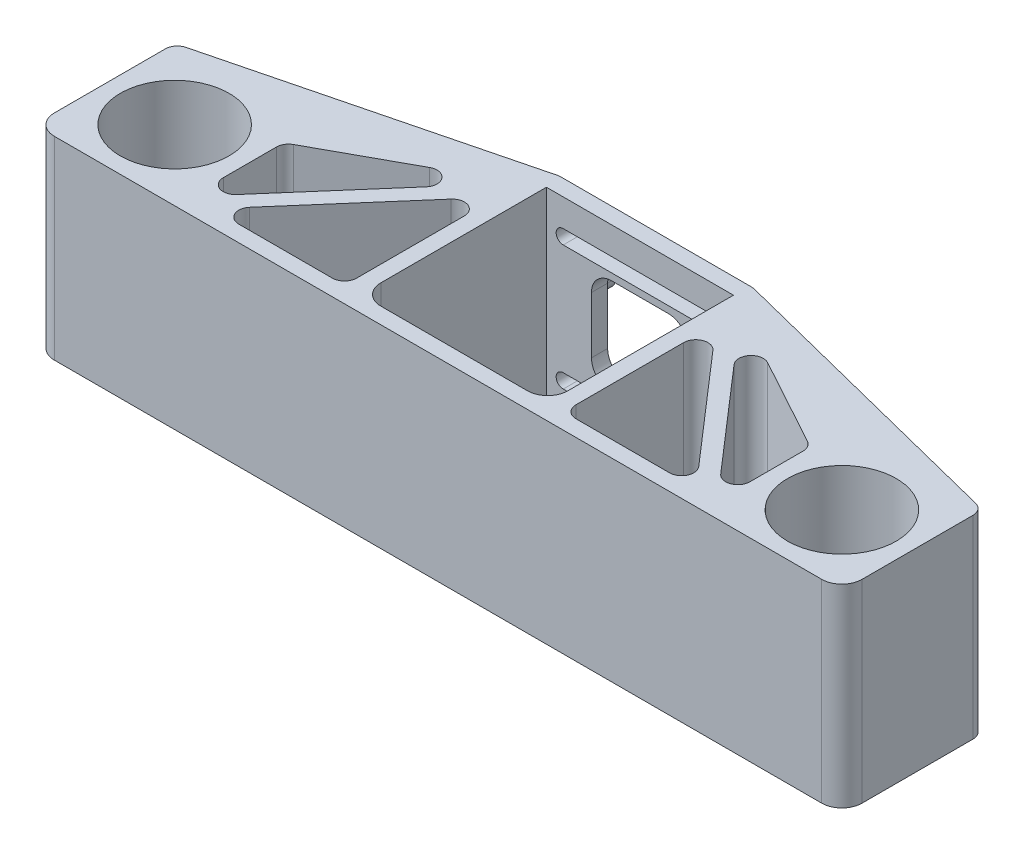
SolidWorks part; units mm, degrees
ref_plane "Front Plane" through (0, 0, 0) normal (0, 0, 1) x (1, 0, 0)
ref_plane "Top Plane" through (0, 0, 0) normal (0, 1, 0) x (1, 0, 0)
ref_plane "Right Plane" through (0, 0, 0) normal (1, 0, 0) x (0, 0, -1)
sketch "Sketch2" plane through (0, 0, 0) normal (0, 1, 0) x (1, 0, 0)
  line L0 (-17.4, -17.4) -> (82.6, -17.4) construction
  line L1 (-17.4, -17.4) -> (17.4, -17.4)
  line L2 (-17.4, -17.4) -> (-17.4, 17.4)
  line L5 (0, 17.4) -> (0, -17.4) construction
  line L6 (-17.4, 0) -> (17.4, 9.5816) construction
  line L7 (82.6, -17.4) -> (82.6, 36.6) construction
  line L8 (17.4, -13.4) -> (17.4, 9.5816)
  line L9 (82.6, 36.6) -> (58.6, 36.6)
  line L10 (82.6, 36.6) -> (82.6, 32.6)
  line L11 (82.6, 32.6) -> (59.447, 32.6)
  line L13 (17.4, 9.5816) -> (55.447, 30.4102)
  line L14 (58.6, 36.6) -> (-17.4, 17.4)
  line L15 (17.4, -17.4) -> (82.6, -17.4)
  line L16 (82.6, -17.4) -> (82.6, -13.4)
  line L17 (82.6, -13.4) -> (59.447, -13.4)
  line L18 (59.447, 32.6) -> (59.447, -13.4)
  line L20 (55.447, -13.4) -> (55.447, 24.3099)
  line L22 (55.447, 30.4102) -> (17.4, -13.4)
  line L23 (22.6979, -13.4) -> (55.447, 24.3099)
  line L24 (55.447, -13.4) -> (22.6979, -13.4)
  circle A0 centre (0, 0) radius 13.45
  point P0 (0, 0)
  dimension "D3" = 26.9
  dimension "D8" = 17.4
  dimension "D9" = 17.4
  dimension "D1" = 34.8
  dimension "D2" = 34.8
  dimension "D4" = 100
  dimension "D5" = 54
  dimension "D6" = 24
  dimension "D7" = 4
  dimension "D10" = 4
  dimension "D11" = 4
  dimension "D12" = 4
extrude "Boss-Extrude1" add sketch "Sketch2" along normal blind 48
sketch3d "3DSketch1"
  line L0 (82.6, 0, -36.6) -> (82.6, 0, -32.6) construction
  line L1 (82.6, 0, -32.6) -> (82.6, 48, -32.6) construction
ref_plane "Plane1" through (82.6, 0, 0) normal (1, 0, 0) x (0, 0, -1)
mirror "Mirror1" about plane through (82.6, 0, 0) normal (1, 0, 0) of "Boss-Extrude1"
sketch "Sketch4" plane through (0, 0, -36.6) normal (0, 0, -1) x (-1, 0, 0)
  line L0 (-106.6, 24) -> (-58.6, 24) construction
  line L1 (-58.6, 48) -> (-58.6, 0) construction
  line L2 (-101.6, 8.55) -> (-63.6, 8.55) construction
  line L3 (-101.6, 10.3) -> (-63.6, 10.3)
  line L4 (-82.6, 0) -> (-82.6, 48) construction
  line L5 (-101.6, 6.8) -> (-63.6, 6.8)
  line L6 (-101.6, 39.45) -> (-63.6, 39.45) construction
  line L7 (-101.6, 37.7) -> (-63.6, 37.7)
  line L8 (-101.6, 41.2) -> (-63.6, 41.2)
  line L10 (-89.6, 12) -> (-75.6, 12)
  line L11 (-94.6, 17) -> (-94.6, 31)
  line L12 (-89.6, 36) -> (-75.6, 36)
  line L13 (-70.6, 17) -> (-70.6, 31)
  line L14 (-94.6, 12) -> (-70.6, 36) construction
  line L15 (-94.6, 36) -> (-70.6, 12) construction
  arc A0 (-101.6, 10.3) -> (-101.6, 6.8) centre (-101.6, 8.55) ccw
  arc A1 (-63.6, 6.8) -> (-63.6, 10.3) centre (-63.6, 8.55) ccw
  arc A2 (-101.6, 37.7) -> (-101.6, 41.2) centre (-101.6, 39.45) cw
  arc A3 (-63.6, 41.2) -> (-63.6, 37.7) centre (-63.6, 39.45) cw
  arc A5 (-94.6, 17) -> (-89.6, 12) centre (-89.6, 17) ccw
  arc A6 (-75.6, 12) -> (-70.6, 17) centre (-75.6, 17) ccw
  arc A7 (-70.6, 31) -> (-75.6, 36) centre (-75.6, 31) ccw
  arc A8 (-94.6, 31) -> (-89.6, 36) centre (-89.6, 31) cw
  circle A9 centre (-82.6, 24) radius 12 construction
  point P5 (-82.6, 24)
  point P7 (-82.6, 8.55)
  point P10 (-82.6, 24)
  point P17 (-82.6, 39.45)
  dimension "D4" = 24
  dimension "D6" = 5
  dimension "D1" = 15.45
  dimension "D2" = 1.75
  dimension "D3" = 38
  dimension "D5" = 24
extrude "Cut-Extrude1" cut sketch "Sketch4" against normal blind 10
ref_plane "Plane2" through (0, 0, -36.6) normal (0, 0, -1) x (-1, 0, 0)
sketch "Sketch5" plane through (0, 0, -36.6) normal (0, 0, -1) x (-1, 0, 0)
  line L0 (-107.3963, 24) -> (-21.5979, 24) construction
  line L1 (-82.6, 2.2) -> (-82.6, -2.2) construction
  line L2 (-106.6, 24) -> (-58.6, 24) construction
  line L3 (-59.6, 31) -> (-45.6, 31)
  line L4 (-59.6, 31) -> (-59.6, 17)
  line L5 (-59.6, 17) -> (-45.6, 17)
  line L6 (-45.6, 31) -> (-45.6, 17)
  line L7 (-59.6, 31) -> (-45.6, 17) construction
  line L8 (-59.6, 17) -> (-45.6, 31) construction
  circle A0 centre (-52.6, 24) radius 4.1
  dimension "D1" = 8.2
  dimension "D2" = 30
  dimension "D3" = 14
  dimension "D4" = 14
extrude "Boss-Extrude2" add sketch "Sketch5" along normal blind 13 and the other way blind 4
fillet "Fillet1" radius 3 4 edges at (59.6, 31, -43.1) (59.6, 17, -43.1) (45.6, 31, -41.4579) (45.6, 17, -41.4579)
sketch "Sketch6" plane through (0, 0, -36.6) normal (0, 0, -1) x (-1, 0, 0)
  circle A0 centre (-52.6, 24) radius 4.1 construction
  circle A1 centre (-52.6, 24) radius 4.1
fillet "Fillet2" radius 5 4 edges at (105.753, 24, 13.4) (59.447, 24, 13.4) (182.6, 24, 17.4) (-17.4, 24, 17.4)
fillet "Fillet3" radius 3 17 edges at (106.6, 24, -36.6) (58.6, 8.882, -36.6) (58.6, 39.118, -36.6) (55.447, 24, 13.4) (22.6979, 24, 13.4) (17.4, 24, -9.5816) (55.447, 24, -30.4102) (55.447, 24, -24.3099) (109.753, 24, 13.4) (142.5021, 24, 13.4) (109.753, 24, -24.3099) (109.753, 24, -30.4102) (147.8, 24, -9.5816) (147.8, 24, 13.4) (182.6, 24, -17.4) (-17.4, 24, -17.4) (17.4, 24, 13.4)
